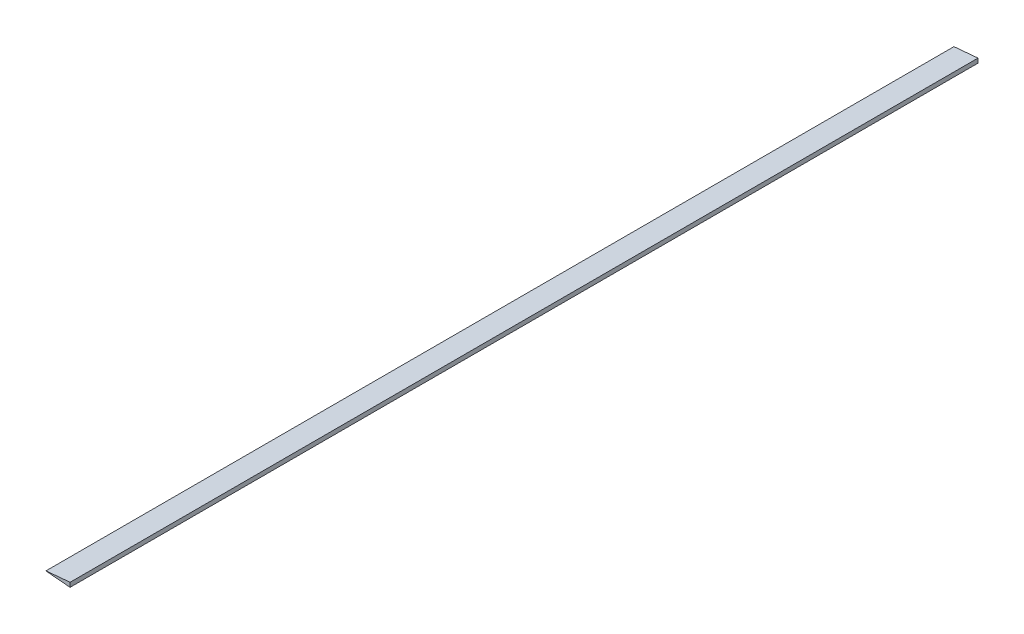
SolidWorks part; units mm, degrees
ref_plane "Front Plane" through (0, 0, 0) normal (0, 0, 1) x (1, 0, 0)
ref_plane "Top Plane" through (0, 0, 0) normal (0, 1, 0) x (1, 0, 0)
ref_plane "Right Plane" through (0, 0, 0) normal (1, 0, 0) x (0, 0, -1)
sketch "Sketch1" plane through (0, 0, 0) normal (0, 0, 1) x (1, 0, 0)
  line L0 (-52.9207, 2.0768) -> (-52.9207, -2.0768)
  line L1 (-75.601, 0.0714) -> (-75.601, -0.0714)
  spline S0 degree 3 poles (-52.9207, 2.0768) (-53.0056, 2.0709) (-54.266, 1.9819) (-56.6322, 1.7987) (-59.9385, 1.5347) (-63.0021, 1.2755) (-65.7896, 1.0291) (-68.2704, 0.8007) (-70.4174, 0.5958) (-72.2071, 0.4197) (-73.6197, 0.277) (-74.64, 0.172) (-75.2566, 0.1076) (-75.532, 0.0787) (-75.601, 0.0714) knots 0 0 0 0 0.011212 0.166483 0.312686 0.448211 0.571563 0.681381 0.776452 0.855723 0.918312 0.963525 0.990856 1 1 1 1
  spline S1 degree 3 poles (-52.9207, -2.0768) (-53.0056, -2.0709) (-54.266, -1.9819) (-56.6322, -1.7987) (-59.9385, -1.5347) (-63.0021, -1.2755) (-65.7896, -1.0291) (-68.2704, -0.8007) (-70.4174, -0.5958) (-72.2071, -0.4197) (-73.6197, -0.277) (-74.64, -0.172) (-75.2566, -0.1076) (-75.532, -0.0787) (-75.601, -0.0714) knots 0 0 0 0 0.011212 0.166483 0.312686 0.448211 0.571563 0.681381 0.776452 0.855723 0.918312 0.963525 0.990856 1 1 1 1
extrude "Boss-Extrude1" add sketch "Sketch1" along normal mid plane 855.4
